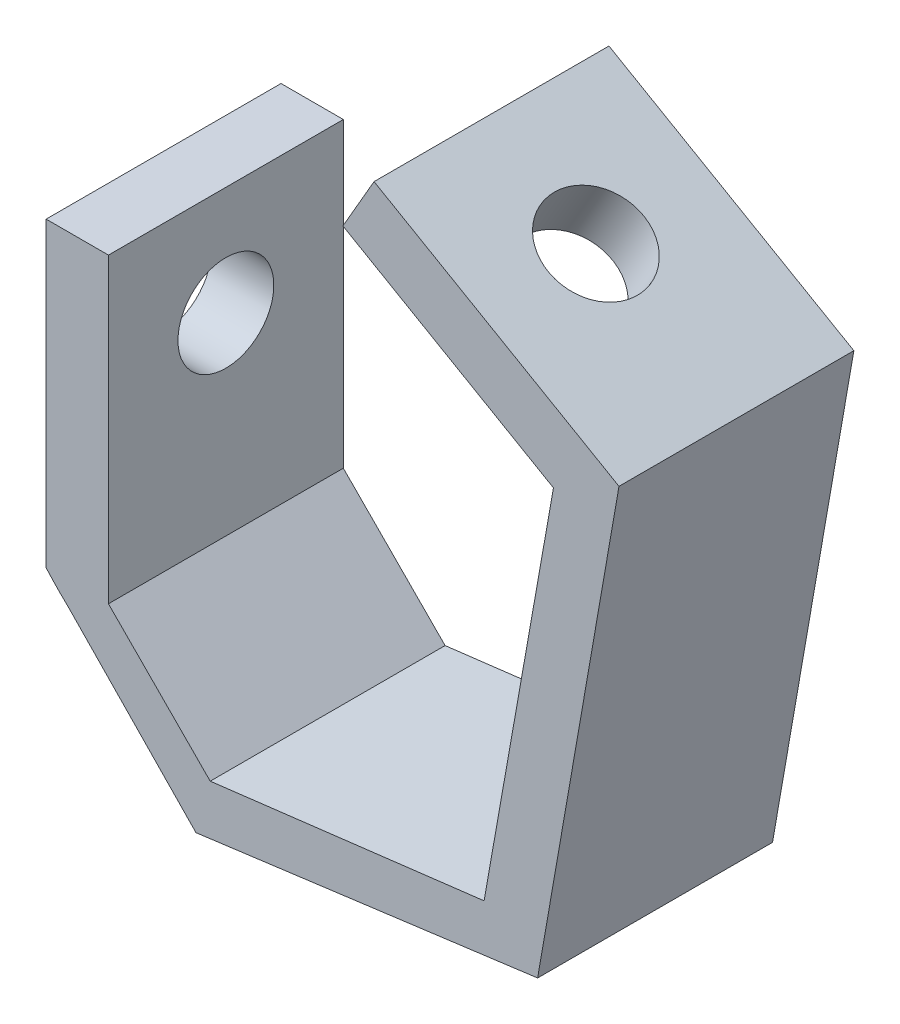
SolidWorks part; units mm, degrees
ref_plane "Front Plane" through (0, 0, 0) normal (0, 0, 1) x (1, 0, 0)
ref_plane "Top Plane" through (0, 0, 0) normal (0, 1, 0) x (1, 0, 0)
ref_plane "Right Plane" through (0, 0, 0) normal (1, 0, 0) x (0, 0, -1)
sketch "Sketch1" plane through (0, 0, 0) normal (0, 0, 1) x (1, 0, 0)
  line L0 (0, 0) -> (-93.9629, 0)
  line L1 (0, 0) -> (0, 93.9629)
  line L2 (0, 0) -> (67.4537, 116.8333)
  line L3 (0, 0) -> (-56, 0)
  line L4 (0, 0) -> (32.75, 56.7247)
  line L5 (-56, 0) -> (-56, 45)
  line L6 (32.75, 56.7247) -> (44.0083, 50.2247)
  line L7 (44.0083, 50.2247) -> (7.5056, -13)
  line L8 (0, 0) -> (0, -13)
  line L9 (0, -13) -> (7.5056, -13)
  line L10 (0, -13) -> (-56, -13)
  line L11 (-56, -13) -> (-56, 0)
  line L12 (-56, 45) -> (-69, 45)
  line L13 (-69, 45) -> (-69, -13)
  line L14 (-69, -13) -> (-56, -13)
  line L15 (44.0083, 50.2247) -> (50.5083, 61.483)
  line L16 (44.0083, 50.2247) -> (0, 75.6329)
  line L17 (50.5083, 61.483) -> (3.743, 88.483)
  line L18 (32.75, 56.7247) -> (-2.757, 77.2247)
  line L19 (3.743, 88.483) -> (-2.757, 77.2247)
  line L20 (-56, 45) -> (-56, 56.7247)
  line L21 (-2.757, 77.2247) -> (-7.0872, 79.7247)
  line L22 (-56, 45) -> (-69, 45)
  line L23 (-56, 45) -> (-56, 50)
  line L24 (-56, 50) -> (-69, 50)
  line L25 (-69, 45) -> (-69, 50)
  line L26 (-7.0872, 79.7247) -> (10.3995, 110.0125)
  line L27 (3.743, 88.483) -> (-0.5872, 90.983)
  circle A0 centre (0, 0) radius 93.9629
  dimension "D1" = 30
  dimension "D2" = 56
  dimension "D3" = 65.5
  dimension "D4" = 45
  dimension "D5" = 13
  dimension "D6" = 13
  dimension "D7" = 13
  dimension "D8" = 13
  dimension "D9" = 90
  dimension "D10" = 54
  dimension "D11" = 5
  dimension "D12" = 5
extrude "Boss-Extrude3" add sketch "Sketch1" along normal blind 49 contours L17 L19 L1 L16 L2 | L1 L27 L26 L21 L19 | L19 L27 L1 | L1 L19 L18 | L15 L17 L2 L6 | L8 L9 L7 L6 L2 | L11 L10 L8 L0 | L13 L14 L11 L0 | L12 L13 L0 L5 | L25 L12 L20 L24 region at (-28, -6.5, 0) region at (20.1921, 21.751, 0) region at (-62.5, -6.5, 0) region at (-62.5, 22.5, 0) region at (-0.919, 78.2858, 0) region at (18.5674, 72.5087, 0) region at (41.6292, 59.1038, 0) region at (-62.5, 47.5, 0) region at (-2.6395, 83.1302, 0) region at (1.2477, 87.0423, 0)
sketch "Sketch5" plane through (-69, 0, 0) normal (-1, 0, 0) x (0, 0, 1)
  line L0 (0, -13) -> (0, 0)
  line L1 (0, 50) -> (0, -13) construction
  line L2 (0, 50) -> (0, 45)
  line L3 (0, 0) -> (0, 5)
  line L4 (0, 5) -> (49, 5)
  line L5 (49, 50) -> (49, -13) construction
  line L6 (24.5, 5) -> (24.5, 45)
  line L9 (0, 45) -> (49, 45)
  circle A0 centre (24.5, 25) radius 19
  dimension "D4" = 38
  dimension "D1" = 5
  dimension "D2" = 13
  dimension "D3" = 5
extrude "Cut-Extrude2" cut sketch "Sketch5" against normal blind 49 contours L6 A0 | L6 A0 region at (-69, 25, 16.4361) region at (-69, 25, 32.5639)
sketch "Sketch6" plane through (39.25, 67.983, 0) normal (0.5, 0.866, 0) x (0.866, -0.5, 0)
  line L0 (13, -49) -> (0, -49)
  line L1 (13, -49) -> (-46, -49) construction
  line L2 (13, -49) -> (13, 0)
  line L3 (-46, -49) -> (-41, -49)
  line L4 (-41, -49) -> (-41, 0)
  line L5 (13, 0) -> (-46, 0) construction
  line L6 (-41, -24.5) -> (-0.7, -24.5)
  line L7 (0, -49) -> (-0.7, -49)
  line L8 (-0.7, -49) -> (-0.7, 0)
  circle A0 centre (-20.85, -24.5) radius 19
  dimension "D4" = 38
  dimension "D1" = 13
  dimension "D2" = 5
  dimension "D3" = 0.7
extrude "Cut-Extrude3" cut sketch "Sketch6" against normal blind 49 contours L6 A0 | L6 A0 region at (21.1934, 78.408, 16.4361) region at (21.1934, 78.408, 32.5639)
sketch "Sketch9" plane through (39.25, 67.983, 0) normal (0.5, 0.866, 0) x (0.866, -0.5, 0)
  circle A0 centre (-20.85, -24.5) radius 10
  circle A1 centre (-20.85, -24.5) radius 19
  dimension "D1" = 20
extrude "Boss-Extrude4" add sketch "Sketch9" against normal blind 13
sketch "Sketch11" plane through (-69, 0, 0) normal (-1, 0, 0) x (0, 0, 1)
  circle A0 centre (24.5, 25) radius 19
  circle A1 centre (24.5, 25) radius 10
  dimension "D1" = 20
extrude "Boss-Extrude5" add sketch "Sketch11" against normal blind 13
sketch "Sketch12" plane through (0, 0, 49) normal (0, 0, 1) x (1, 0, 0)
  line L3 (50.5083, 61.483) -> (32.75, 56.7247)
  line L4 (-56, 0) -> (-69, -13)
  arc A1 (-69, -13) -> (50.5083, 61.483) centre (-15.5218, 34.3114) ccw
  arc A3 (-56, 0) -> (32.75, 56.7247) centre (-11.4527, 28.0927) ccw
extrude "Boss-Extrude6" add sketch "Sketch12" against normal blind 58
sketch "Sketch13" plane through (0, 0, 49) normal (0, 0, 1) x (1, 0, 0)
  line L0 (32.75, 56.7247) -> (39.3165, 42.0982)
  line L1 (39.3165, 42.0982) -> (7.5056, -13)
  line L2 (7.5056, -13) -> (-44.3928, -13)
  line L3 (-44.3928, -13) -> (-56, 0)
  line L4 (-56, 0) -> (0, 0)
  line L5 (0, 0) -> (32.75, 56.7247)
extrude "Cut-Extrude4" cut sketch "Sketch13" against normal blind 58
sketch "Sketch15" plane through (-56, 0, 0) normal (1, 0, 0) x (0, 0, -1)
  circle A0 centre (-24.5, 25) radius 10
  circle A1 centre (-24.5, 25) radius 10
ref_axis "Axis3" through (-56, 25, 24.5) along (-1, 0, 0)
ref_axis "Axis4" through (10.3632, 59.6497, 24.5) along (0.5, 0.866, 0)
sketch "Sketch16" plane through (-69, 0, 0) normal (-1, 0, 0) x (0, 0, 1)
  line L0 (-20.0677, -13) -> (-20.0677, 53.2335)
  line L2 (0, -13) -> (0, 53.2335)
  line L6 (0, -13) -> (0, -105.8441)
  line L7 (0, -105.8441) -> (-20.0677, -105.8441)
  line L8 (-20.0677, -13) -> (-20.0677, -105.8441)
  line L10 (0, 53.2335) -> (0, 98.9908)
  line L11 (0, 98.9908) -> (-20.0677, 98.9908)
  line L12 (-20.0677, 53.2335) -> (-20.0677, 98.9908)
extrude "Cut-Extrude5" cut sketch "Sketch16" against normal blind 184
sketch "Sketch17" plane through (-69, 0, 0) normal (-1, 0, 0) x (0, 0, 1)
  arc A2 (14.5669, 26.155) -> (34.4331, 26.155) centre (24.5, 27.31) ccw
  arc A3 (14.5669, 26.155) -> (34.4331, 26.155) centre (24.5, 25) ccw
  arc A4 (14.5669, 26.155) -> (34.4331, 26.155) centre (24.5, 27.31) ccw
  circle M6 centre (24.5, 25) radius 10
extrude "Boss-Extrude7" add sketch "Sketch17" along normal blind 3 and the other way blind 20 contours A2 M6 region at (-69, 17.081, 24.5)
sketch "Sketch18" plane through (0, 0, 0) normal (0, 0, -1) x (-1, 0, 0)
  line L0 (56, 0) -> (56, 50) construction
  line L1 (56, 9.3716) -> (46.6712, 9.3716)
  line L2 (56, 9.3716) -> (56, 30.9459)
  line L3 (56, 30.9459) -> (46.6712, 30.9459)
  line L4 (46.6712, 9.3716) -> (46.6712, 30.9459)
  line L5 (69, 50) -> (69, -13) construction
  line L6 (69, 8.1899) -> (91.5508, 8.1899)
  line L7 (69, 8.1899) -> (69, 30.9459)
  line L8 (69, 30.9459) -> (91.5508, 30.9459)
  line L9 (91.5508, 8.1899) -> (91.5508, 30.9459)
extrude "Cut-Extrude6" cut sketch "Sketch18" against normal blind 535
sketch "Sketch19" plane through (-69, 0, 0) normal (-1, 0, 0) x (0, 0, 1)
  circle A0 centre (24.5, 27.31) radius 10
extrude "Cut-Extrude7" cut sketch "Sketch19" against normal blind 29
sketch "Sketch21" plane through (0, 0, 0) normal (0, 0, -1) x (-1, 0, 0)
  line L0 (69, -13) -> (37.7389, -45.2254)
  line L1 (37.7389, -45.2254) -> (-33.536, -35.8406)
  line L2 (-33.536, -35.8406) -> (-48.13, 47.845)
  line L3 (-22.3631, -27.4794) -> (-36.8407, 54.3629)
  line L4 (56, -13) -> (56, 0)
  line L5 (-36.8407, 54.3629) -> (-48.13, 47.845)
  line L6 (37.7389, -31.4616) -> (56, -13)
  line L8 (37.7389, -31.4616) -> (34.7689, -34.4316)
  line L9 (69, -13) -> (56, -13)
  line L13 (-32.75, 56.7247) -> (-36.8407, 54.3629)
  line L14 (37.7389, -45.2254) -> (46.7906, -35.8945)
  line L16 (34.7689, -34.4316) -> (-22.3631, -27.4794)
  line L20 (69, -13) -> (56, -13)
  arc M5 (44.3928, -13) -> (-39.3165, 42.0982) centre (11.4527, 28.0927) cw
  line M6 (-39.3165, 42.0982) -> (-32.75, 56.7247)
  arc M10 (-50.5083, 61.483) -> (69, -13) centre (15.5218, 34.3114) ccw
  dimension "D2" = 13
  dimension "D5" = 13
extrude "Boss-Extrude12" add sketch "Sketch21" along normal blind 284 contours L8 L16 L0 L9 L6 M10 | L16 L3 L2 L1 L0 M10 | L3 L5 L2 M10 M5 M6 | L3 M5 M6 region at (-41.4993, -39.8174, 0) region at (-23.9231, -35.6693, 0) region at (41.9405, 17.2641, 0) region at (34.6922, 19.6776, 0)
sketch "Sketch23" plane through (0, 0, 0) normal (0, 0, -1) x (-1, 0, 0)
  line L0 (-37.4133, -13.6067) -> (-50.5083, 61.483)
  line L1 (-50.5083, 61.483) -> (-79.984, 56.3427)
  line L2 (-79.984, 56.3427) -> (-66.889, -18.747)
  line L3 (-66.889, -18.747) -> (-37.4133, -13.6067)
  line L4 (-36.8137, 54.2104) -> (-32.75, 56.7247)
  line L5 (-35.9841, 49.5209) -> (-36.8407, 54.3629) construction
  line L7 (-35.9841, 49.5209) -> (-36.8137, 54.2104)
  line L8 (56, -13) -> (56, 0)
  line L9 (56, 0) -> (-32.75, 56.7247)
  line L10 (56, -13) -> (34.7689, -34.4316)
  line L11 (34.7689, -34.4316) -> (-22.3631, -27.4794)
  line L12 (-22.3631, -27.4794) -> (-36.8137, 54.2104)
  line M5 (-35.9841, 49.5209) -> (-32.75, 56.7247)
extrude "Cut-Extrude9" cut sketch "Sketch23" against normal blind 284 contours L12 L11 L10 L8 L9 M5 | L0 L1 L2 L3 region at (-5.5308, 2.9325, 0)
sketch "Sketch26" plane through (0, 0, 0) normal (0, 0, 1) x (1, 0, 0)
  line L0 (-69, -13) -> (-37.7389, -45.2254)
  line L1 (-37.7389, -45.2254) -> (33.536, -35.8406)
  line L2 (33.536, -35.8406) -> (37.4133, -13.6067)
  line L3 (35.9841, 49.5209) -> (22.3631, -27.4794)
  line L4 (22.3631, -27.4794) -> (-34.7689, -34.4316)
  line L5 (-34.7689, -34.4316) -> (-56, -13)
  line L6 (-56, -13) -> (-70.0229, -13)
  line L7 (48.13, 47.845) -> (37.4133, -13.6067)
  line L8 (48.13, 47.845) -> (35.9841, 49.5209)
  line M1 (33.536, -35.8406) -> (37.4133, -13.6067)
  arc M2 (37.4133, -13.6067) -> (22.6155, -26.0527) centre (-15.5218, 34.3114) cw
  line M3 (22.6155, -26.0527) -> (22.3631, -27.4794)
  line M4 (22.3631, -27.4794) -> (19.6901, -27.8046)
  arc M5 (19.6901, -27.8046) -> (-64.4355, -17.7053) centre (-15.5218, 34.3114) cw
  line M6 (-64.4355, -17.7053) -> (-37.7389, -45.2254)
  line M7 (-37.7389, -45.2254) -> (33.536, -35.8406)
extrude "Boss-Extrude13" add sketch "Sketch26" along normal blind 154 contours L7 L8 L3 M2 | M7 M1 M2 M3 M4 M5 M6 region at (-24.1597, -37.6407, 0) region at (35.737, 13.9215, 0)
sketch "Sketch27" plane through (39.25, 67.983, 0) normal (0.5, 0.866, 0) x (0.866, -0.5, 0)
  line L1 (13, -49) -> (-173.2884, -49)
  line L4 (-173.2884, -49) -> (-173.2884, -127.5137)
  line L5 (13, -49) -> (112.2153, -49)
  line L8 (112.2153, -49) -> (112.2153, -127.5137)
  line L9 (13, 0) -> (-173.2884, 0)
  line L12 (-173.2884, 0) -> (-173.2884, 168.4775)
  line L13 (13, 0) -> (177.5909, 0)
  line L15 (13, 352.4182) -> (177.5909, 352.4182)
  line L16 (177.5909, 0) -> (177.5909, 352.4182)
  line L17 (13, 352.4182) -> (-178.9571, 352.4182)
  line L19 (-173.2884, 168.4775) -> (-178.9571, 168.4775)
  line L20 (-178.9571, 352.4182) -> (-178.9571, 168.4775)
  line L21 (-173.2884, -49) -> (112.2153, -49)
  line L22 (-173.2884, -49) -> (-173.2884, -252.6626)
  line L23 (-173.2884, -252.6626) -> (112.2153, -252.6626)
  line L24 (112.2153, -49) -> (112.2153, -252.6626)
  line M1 (13, 0) -> (-46, 0)
  line M3 (-46, -49) -> (13, -49)
extrude "Cut-Extrude12" cut sketch "Sketch27" against normal blind 199 contours L17 L20 L19 L12 L9 L13 L16 L15 M1 | L24 L8 L5 L1 L4 L22 L23 M3 region at (12.8046, 83.2513, 150.8313) region at (39.822, 67.6527, -176.9135)
sketch "Sketch28" plane through (0, 0, 49) normal (0, 0, 1) x (1, 0, 0)
  line L1 (32.75, 56.7247) -> (36.8407, 54.3629)
  line L3 (35.9841, 49.5209) -> (36.8407, 54.3629)
  line L4 (32.75, 56.7247) -> (35.9841, 49.5209)
extrude "Cut-Extrude13" cut sketch "Sketch28" against normal blind 73
